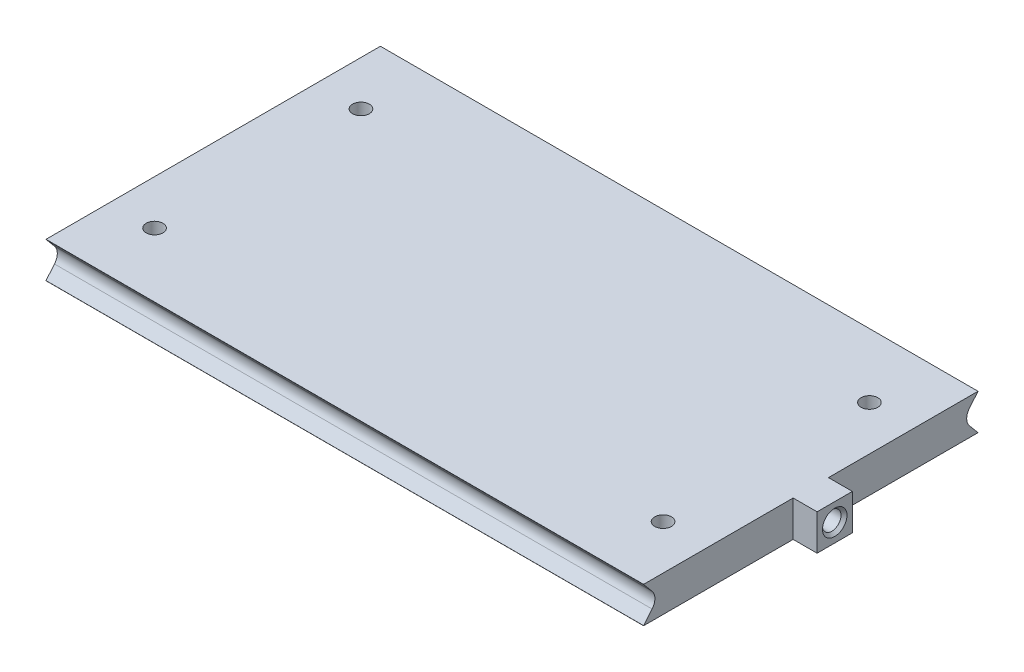
SolidWorks part; units mm, degrees
ref_plane "Płaszczyzna przednia" through (0, 0, 0) normal (0, 0, 1) x (1, 0, 0)
ref_plane "Płaszczyzna górna" through (0, 0, 0) normal (0, 1, 0) x (1, 0, 0)
ref_plane "Płaszczyzna prawa" through (0, 0, 0) normal (1, 0, 0) x (0, 0, -1)
sketch "Szkic1" plane through (0, 0, 0) normal (0, 1, 0) x (1, 0, 0)
  line L1 (-49.95, -27.95) -> (49.95, -27.95)
  line L2 (-49.95, -27.95) -> (-49.95, 27.95)
  line L3 (-49.95, 27.95) -> (49.95, 27.95)
  line L4 (49.95, -27.95) -> (49.95, 27.95)
  line L5 (-49.95, -27.95) -> (49.95, 27.95) construction
  line L6 (-49.95, 27.95) -> (49.95, -27.95) construction
  point P0 (0, 0)
  dimension "D1" = 99.9
  dimension "D2" = 55.9
extrude "Dodanie-wyciągnięcie1" add sketch "Szkic1" along normal blind 6
sketch "Szkic2" plane through (0, 6, 0) normal (0, 1, 0) x (1, 0, 0)
  line L1 (-42.5, -17.25) -> (42.5, -17.25) construction
  line L2 (-42.5, -17.25) -> (-42.5, 17.25) construction
  line L3 (-42.5, 17.25) -> (42.5, 17.25) construction
  line L4 (42.5, -17.25) -> (42.5, 17.25) construction
  line L5 (-42.5, -17.25) -> (42.5, 17.25) construction
  line L6 (-42.5, 17.25) -> (42.5, -17.25) construction
  circle A0 centre (-42.5, 17.25) radius 1.4
  circle A1 centre (-42.5, -17.25) radius 1.4
  circle A2 centre (42.5, -17.25) radius 1.4
  circle A3 centre (42.5, 17.25) radius 1.4
  point P0 (0, 0)
  dimension "D1" = 2.8
  dimension "D2" = 2.8
  dimension "D3" = 2.8
  dimension "D4" = 2.8
  dimension "D5" = 85
  dimension "D6" = 34.5
extrude "Wytnij-wyciągnięcie1" cut sketch "Szkic2" against normal through all
sketch "Szkic3" plane through (0, 0, 0) normal (0, -1, 0) x (1, 0, 0)
  circle A0 centre (-42.5, 17.25) radius 3
  circle A1 centre (-42.5, -17.25) radius 3
  circle A2 centre (42.5, 17.25) radius 3
  circle A3 centre (42.5, -17.25) radius 3
  dimension "D1" = 6
  dimension "D2" = 6
  dimension "D3" = 6
  dimension "D4" = 6
extrude "Wytnij-wyciągnięcie2" cut sketch "Szkic3" against normal blind 3
sketch "Szkic5" plane through (-49.95, 0, 0) normal (-1, 0, 0) x (0, 0, 1)
  line L0 (-27.95, 0.0206) -> (-27.95, 5.9794)
  line L1 (-27.95, 6) -> (-27.95, 0) construction
  line L2 (-27.95, 5.9794) -> (-25.45, 3)
  line L3 (-25.45, 3) -> (-27.95, 0.0206)
  point P5 (-27.95, 3)
  point P7 (-27.95, 3)
  dimension "D1" = 40
  dimension "D2" = 40
  dimension "D3" = 2.5
extrude "Wytnij-wyciągnięcie6" cut sketch "Szkic5" against normal through all
fillet "Zaokrąglenie3" radius 2 1 edges at (0, 3, -25.45)
mirror "Lustro2" about plane through (0, 0, 0) normal (0, 0, 1) of "Zaokrąglenie3", "Wytnij-wyciągnięcie6"
sketch "Szkic6" plane through (-49.95, 0, 0) normal (-1, 0, 0) x (0, 0, 1)
  line L0 (0, 6) -> (0, 0) construction
  line L1 (-27.95, 6) -> (27.95, 6) construction
  circle A0 centre (0, 3) radius 2
  dimension "D1" = 4
extrude "Wytnij-wyciągnięcie3" cut sketch "Szkic6" against normal blind 1
fillet "Zaokrąglenie2" radius 2 1 edges at (-48.95, 3, 2)
sketch "Szkic7" plane through (49.95, 0, 0) normal (1, 0, 0) x (0, 0, -1)
  line L0 (2.95, 6) -> (2.95, 0)
  line L1 (2.95, 6) -> (-2.95, 6)
  line L2 (2.95, 0) -> (-2.95, 0)
  line L3 (-2.95, 6) -> (-2.95, 0)
  line L4 (2.95, 6) -> (-2.95, 0) construction
  line L5 (2.95, 0) -> (-2.95, 6) construction
  point P0 (0, 0)
  point P1 (0, 3)
  dimension "D1" = 6
  dimension "D2" = 5.9
extrude "Dodanie-wyciągnięcie3" add sketch "Szkic7" along normal blind 4
sketch "Szkic8" plane through (53.95, 0, 0) normal (1, 0, 0) x (0, 0, -1)
  line L0 (0, 6) -> (0, 0) construction
  line L1 (2.95, 6) -> (-2.95, 6) construction
  line L2 (-2.95, 0) -> (2.95, 0) construction
  circle A0 centre (0, 3) radius 1.55
  dimension "D1" = 3.1
extrude "Wytnij-wyciągnięcie4" cut sketch "Szkic8" against normal blind 6
chamfer "Sfazowanie1" distance 0.5 angle 45 1 edges at (53.95, 3, -1.55)
equation "\"M2.5_screw\"= 2.8"
equation "\"D2@Szkic2\"=\"M2.5_screw\""
equation "\"M2.5_screw2\"=2.8"
equation "\"D1@Szkic2\"=\"M2.5_screw\""
equation "\"D3@Szkic2\"=\"M2.5_screw\""
equation "\"D4@Szkic2\"=\"M2.5_screw\""
equation "\"M2.5_screw_head\"= 6"
equation "\"D1@Szkic3\"=\"M2.5_screw_head\""
equation "\"D2@Szkic3\"=\"M2.5_screw_head\""
equation "\"D3@Szkic3\"=\"M2.5_screw_head\""
equation "\"D4@Szkic3\"=\"M2.5_screw_head\""
